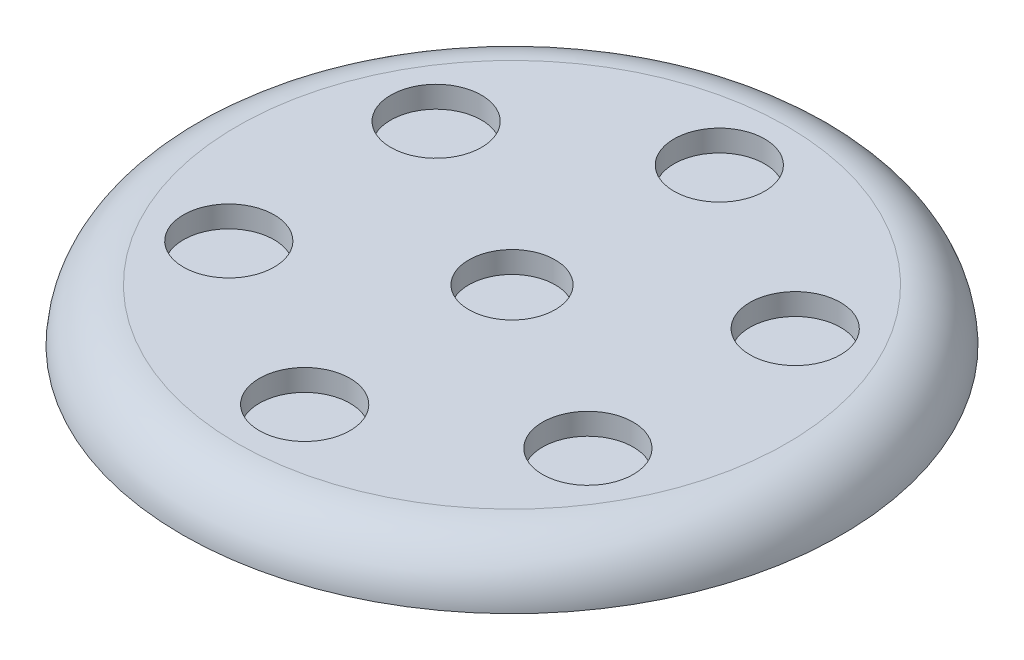
SolidWorks part; units mm, degrees
ref_plane "Plan de face" through (0, 0, 0) normal (0, 0, 1) x (1, 0, 0)
ref_plane "Plan de dessus" through (0, 0, 0) normal (0, 1, 0) x (1, 0, 0)
ref_plane "Plan de droite" through (0, 0, 0) normal (1, 0, 0) x (0, 0, -1)
sketch "Esquisse1" plane through (0, 0, 0) normal (0, 1, 0) x (1, 0, 0)
  circle A0 centre (0, 0) radius 76.3
  dimension "D1" = 152.6
extrude "Boss.-Extru.1" add sketch "Esquisse1" along normal blind 12
fillet "Congé1" radius 12.7 1 edges at (0, 12, 76.3)
sketch "Esquisse2" plane through (0, 12, 0) normal (0, 1, 0) x (1, 0, 0)
  circle A0 centre (0, 0) radius 10
  circle A1 centre (0, 48) radius 10.5
  circle A2 centre (41.5692, 24) radius 10.5
  circle A3 centre (41.5692, -24) radius 10.5
  circle A4 centre (0, -48) radius 10.5
  circle A5 centre (-41.5692, -24) radius 10.5
  circle A6 centre (-41.5692, 24) radius 10.5
  point P18 (0, 0)
  dimension "D1" = 20
  dimension "D2" = 21
  dimension "D3" = 48
  dimension "D4" = 6
extrude "Enlèv. mat.-Extru.1" cut sketch "Esquisse2" against normal blind 5
